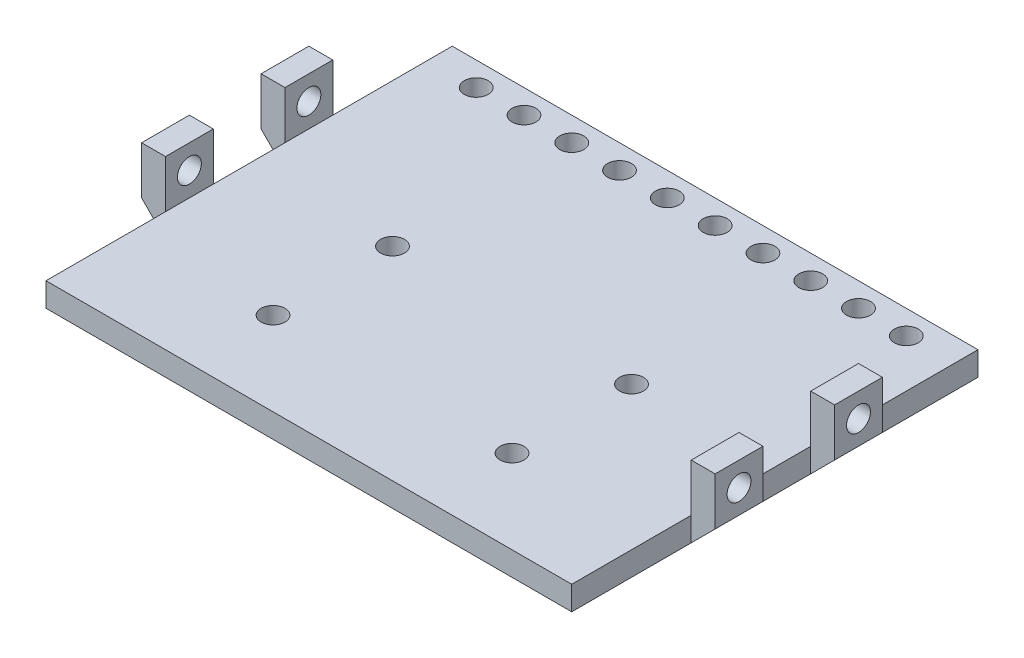
SolidWorks part; units mm, degrees
ref_plane "Front Plane" through (0, 0, 0) normal (0, 0, 1) x (1, 0, 0)
ref_plane "Top Plane" through (0, 0, 0) normal (0, 1, 0) x (1, 0, 0)
ref_plane "Right Plane" through (0, 0, 0) normal (1, 0, 0) x (0, 0, -1)
sketch "Sketch1" plane through (0, 0, 0) normal (0, 1, 0) x (1, 0, 0)
  line L1 (-60, 42.5) -> (60, 42.5)
  line L2 (-60, 42.5) -> (-60, -42.5)
  line L3 (-60, -42.5) -> (60, -42.5)
  line L4 (60, 42.5) -> (60, -42.5)
  line L5 (-60, 42.5) -> (60, -42.5) construction
  line L6 (-60, -42.5) -> (60, 42.5) construction
  point P0 (0, 0)
  dimension "D1" = 120
  dimension "D2" = 85
extrude "Boss-Extrude1" add sketch "Sketch1" along normal blind 5
sketch "Sketch2" plane through (0, 5, 0) normal (0, 1, 0) x (1, 0, 0)
  line L0 (-60, 42.5) -> (-60, -42.5) construction
  line L1 (-60, 17.5) -> (-55, 17.5)
  line L2 (-60, 17.5) -> (-60, 7.5)
  line L3 (-60, 7.5) -> (-55, 7.5)
  line L4 (-55, 17.5) -> (-55, 7.5)
  line L6 (-60, -7.5) -> (-55, -7.5)
  line L7 (-60, -7.5) -> (-60, -17.5)
  line L8 (-60, -17.5) -> (-55, -17.5)
  line L9 (-55, -7.5) -> (-55, -17.5)
  line L10 (-60, 12.5) -> (-55, 12.5) construction
  line L11 (-60, -12.5) -> (-55, -12.5) construction
  line L14 (60, 42.5) -> (-60, 42.5) construction
  line L16 (0, 0) -> (0, -27.3364) construction
  line L17 (60, -12.5) -> (55, -12.5) construction
  line L18 (60, 12.5) -> (55, 12.5) construction
  line L19 (55, -7.5) -> (55, -17.5)
  line L20 (60, -17.5) -> (55, -17.5)
  line L21 (60, -7.5) -> (60, -17.5)
  line L22 (60, -7.5) -> (55, -7.5)
  line L23 (55, 17.5) -> (55, 7.5)
  line L24 (60, 7.5) -> (55, 7.5)
  line L25 (60, 17.5) -> (60, 7.5)
  line L26 (60, 17.5) -> (55, 17.5)
  dimension "D1" = 30
  dimension "D2" = 10
  dimension "D3" = 10
  dimension "D4" = 25
  dimension "D5" = 5
  dimension "D6" = 5
extrude "Boss-Extrude2" add sketch "Sketch2" along normal blind 10
sketch "Sketch3" plane through (-60, 0, 0) normal (-1, 0, 0) x (0, 0, 1)
  line L0 (7.5, 15) -> (17.5, 15) construction
  line L1 (-17.5, 15) -> (-7.5, 15) construction
  line L2 (-17.5, 15) -> (-17.5, 5) construction
  line L3 (7.5, 15) -> (7.5, 5) construction
  circle A0 centre (-12.5, 10) radius 2.5
  circle A1 centre (12.5, 10) radius 2.5
  dimension "D1" = 5
  dimension "D2" = 5
  dimension "D3" = 5
  dimension "D4" = 5
  dimension "D5" = 5
  dimension "D6" = 5
extrude "Cut-Extrude1" cut sketch "Sketch3" against normal through all
sketch "Sketch5" plane through (0, 5, 0) normal (0, 1, 0) x (1, 0, 0)
  line L0 (0, 0) -> (0, -37.502) construction
  line L1 (-60, 42.5) -> (-55, 42.5)
  line L2 (-60, 42.5) -> (-60, 17.5)
  line L3 (-60, 17.5) -> (-55, 17.5)
  line L4 (-55, 42.5) -> (-55, 17.5)
  line L5 (-60, 7.5) -> (-55, 7.5)
  line L6 (-60, 7.5) -> (-60, -7.5)
  line L7 (-60, -7.5) -> (-55, -7.5)
  line L8 (-55, 7.5) -> (-55, -7.5)
  line L9 (-55, -17.5) -> (-60, -17.5)
  line L10 (-55, -17.5) -> (-55, -42.5)
  line L11 (-55, -42.5) -> (-60, -42.5)
  line L12 (-60, -17.5) -> (-60, -42.5)
  line L13 (60, -17.5) -> (60, -42.5)
  line L14 (55, -42.5) -> (60, -42.5)
  line L15 (55, -17.5) -> (55, -42.5)
  line L16 (55, -17.5) -> (60, -17.5)
  line L17 (55, 7.5) -> (55, -7.5)
  line L18 (60, -7.5) -> (55, -7.5)
  line L19 (60, 7.5) -> (60, -7.5)
  line L20 (60, 7.5) -> (55, 7.5)
  line L21 (55, 42.5) -> (55, 17.5)
  line L22 (60, 17.5) -> (55, 17.5)
  line L23 (60, 42.5) -> (60, 17.5)
  line L24 (60, 42.5) -> (55, 42.5)
extrude "Cut-Extrude2" cut sketch "Sketch5" against normal through all
chamfer "Chamfer1" distance 5 angle 45 4 edges at (-60, 0, 12.5) (-60, 0, -12.5) (60, 0, -12.5) (60, 0, 12.5)
sketch "Sketch6" plane through (0, 0, 0) normal (0, -1, 0) x (1, 0, 0)
  line L0 (-55, 42.5) -> (55, 42.5) construction
  circle A0 centre (25, 0) radius 2.5
  circle A1 centre (-25, 0) radius 2.5
  circle A2 centre (25, 25) radius 2.5
  circle A3 centre (-25, 25) radius 2.5
  dimension "D1" = 5
  dimension "D2" = 5
  dimension "D3" = 25
  dimension "D4" = 25
  dimension "D5" = 42.5
  dimension "D6" = 42.5
  dimension "D7" = 2
extrude "Cut-Extrude3" cut sketch "Sketch6" against normal through all
sketch "Sketch7" plane through (0, 0, 0) normal (0, -1, 0) x (1, 0, 0)
  line L0 (55, -42.5) -> (-55, -42.5) construction
  line L1 (-55, -17.5) -> (-55, -42.5) construction
  line L3 (55, -42.5) -> (55, -17.5) construction
  circle A0 centre (-45, -37.5) radius 2.5
  circle A1 centre (-35, -37.5) radius 2.5
  circle A2 centre (-25, -37.5) radius 2.5
  circle A3 centre (-15, -37.5) radius 2.5
  circle A4 centre (-5, -37.5) radius 2.5
  circle A5 centre (5, -37.5) radius 2.5
  circle A6 centre (15, -37.5) radius 2.5
  circle A7 centre (25, -37.5) radius 2.5
  circle A8 centre (35, -37.5) radius 2.5
  circle A9 centre (45, -37.5) radius 2.5
  dimension "D1" = 5
  dimension "D2" = 5
  dimension "D3" = 10
  dimension "D5" = 10
  dimension "D4" = 10
extrude "Cut-Extrude4" cut sketch "Sketch7" against normal blind 10
